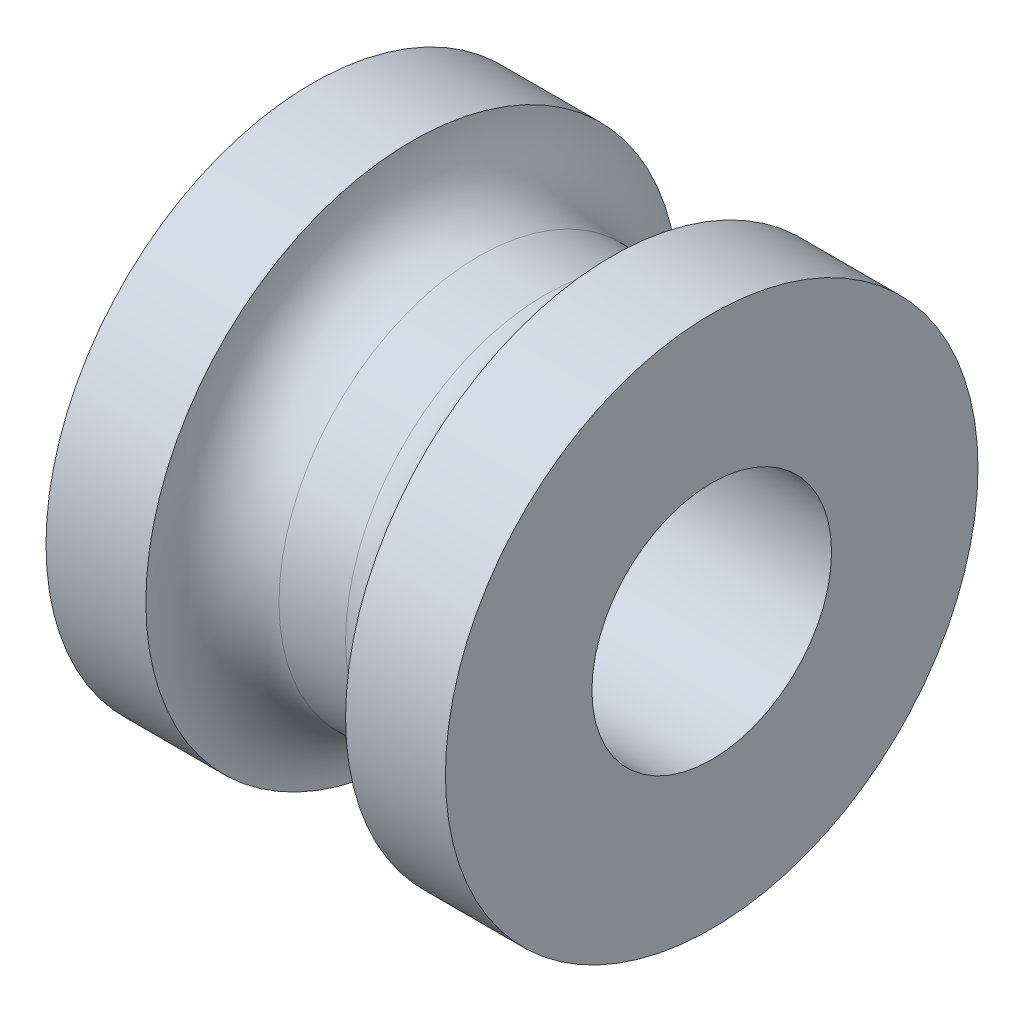
SolidWorks part; units mm, degrees
ref_plane "Front Plane" through (0, 0, 0) normal (0, 0, 1) x (1, 0, 0)
ref_plane "Top Plane" through (0, 0, 0) normal (0, 1, 0) x (1, 0, 0)
ref_plane "Right Plane" through (0, 0, 0) normal (1, 0, 0) x (0, 0, -1)
sketch "Sketch1" plane through (0, 0, 0) normal (1, 0, 0) x (0, 0, -1)
  circle A0 centre (0, 0) radius 4
  dimension "D1" = 8
extrude "Boss-Extrude1" add sketch "Sketch1" along normal blind 1.5
sketch "Sketch2" plane through (1.5, 0, 0) normal (1, 0, 0) x (0, 0, -1)
  circle A0 centre (0, 0) radius 3
  dimension "D1" = 6
extrude "Boss-Extrude2" add sketch "Sketch2" along normal blind 3
sketch "Sketch3" plane through (4.5, 0, 0) normal (1, 0, 0) x (0, 0, -1)
  circle A0 centre (0, 0) radius 4
  dimension "D1" = 8
extrude "Boss-Extrude3" add sketch "Sketch3" along normal blind 1.5
fillet "Fillet1" radius 1 2 edges at (4.5, 0, -3) (1.5, 0, -3)
sketch "Sketch4" plane through (0, 0, 0) normal (-1, 0, 0) x (0, 0, 1)
  circle A0 centre (0, 0) radius 1.8
  dimension "D1" = 3.6
extrude "Cut-Extrude1" cut sketch "Sketch4" against normal through all
equation "\"滑动-垂直孔\"= 0.6"
equation "\"滑动-水平孔\"= 0.3"
equation "\"松动-垂直孔\"= 0.3"
equation "\"松动-水平孔\"= 0.1"
equation "\"正常-垂直孔\"= 0.15"
equation "\"正常-水平孔\"= 0"
equation "\"紧缩-垂直孔\"= 0"
equation "\"紧缩-水平孔\"= - 0.1"
equation "\"D1@Sketch4\"=\"滑动-垂直孔\"+3"
